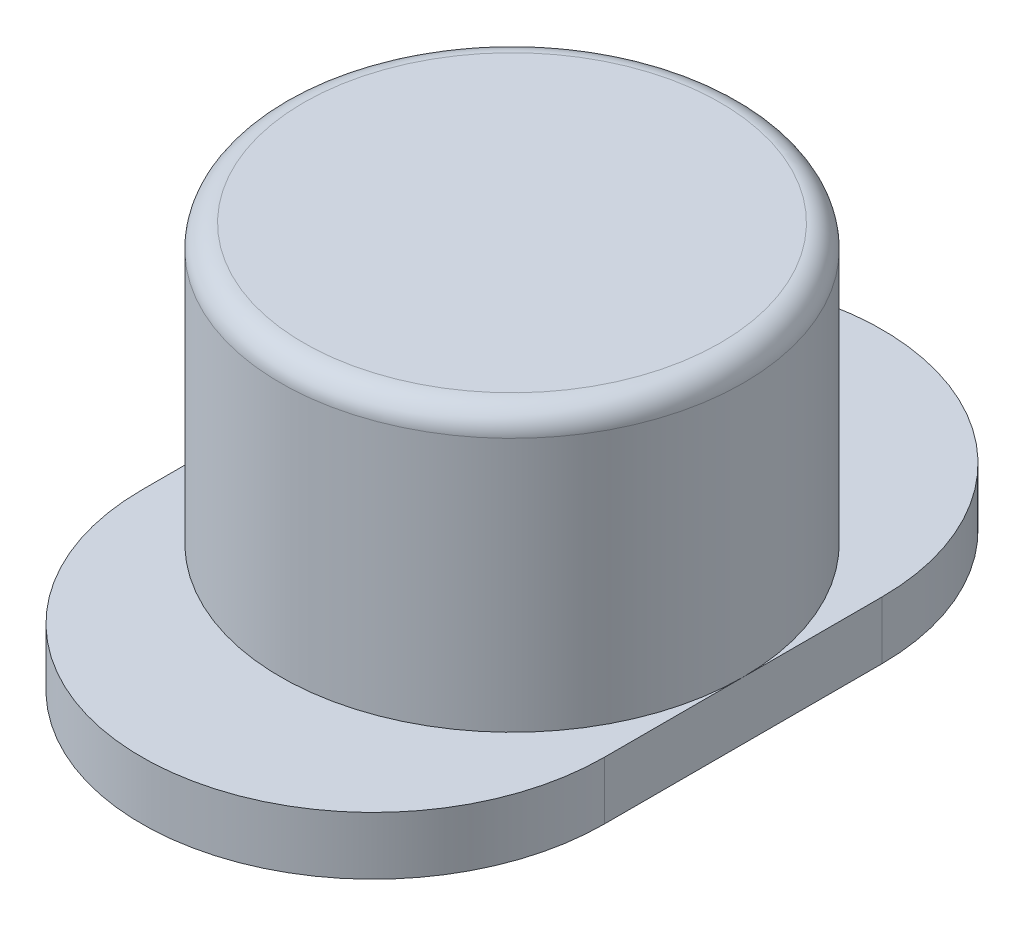
SolidWorks part; units mm, degrees
ref_plane "Front Plane" through (0, 0, 0) normal (0, 0, 1) x (1, 0, 0)
ref_plane "Top Plane" through (0, 0, 0) normal (0, 1, 0) x (1, 0, 0)
ref_plane "Right Plane" through (0, 0, 0) normal (1, 0, 0) x (0, 0, -1)
sketch "Sketch1" plane through (0, 0, 0) normal (0, 0, 1) x (1, 0, 0)
  line L1 (0, 7.25) -> (5, 7.25)
  line L2 (5, 7.25) -> (5, 1.25)
  line L3 (5, 1.25) -> (8, 1.25)
  line L4 (8, 1.25) -> (8, 0)
  line L6 (0, 7.25) -> (0, 6.9292) construction
  line L7 (0, 7.25) -> (0, 0)
  line L10 (0, 0) -> (8, 0)
  dimension "D1" = 5
  dimension "D2" = 3
  dimension "D3" = 6
  dimension "D4" = 1.25
revolve "Revolve1" add sketch "Sketch1" angle 360 about L6
sketch "Sketch2" plane through (0, 0, 0) normal (0, -1, 0) x (1, 0, 0)
  line L1 (-1.75, -1.25) -> (1.75, -1.25)
  line L2 (-1.75, -1.25) -> (-1.75, 1.25)
  line L3 (-1.75, 1.25) -> (1.75, 1.25)
  line L4 (1.75, -1.25) -> (1.75, 1.25)
  line L5 (-1.75, -1.25) -> (1.75, 1.25) construction
  line L6 (-1.75, 1.25) -> (1.75, -1.25) construction
  point P0 (0, 0)
  dimension "D1" = 3.5
  dimension "D2" = 2.5
extrude "Cut-Extrude1" cut sketch "Sketch2" against normal blind 3.5 contours L3 L4 L1 L2
fillet "Fillet1" radius 0.5 1 edges at (-5, 7.25, 0)
sketch "Sketch3" plane through (0, 0, 0) normal (0, 1, 0) x (1, 0, 0)
  line L0 (0, -3) -> (0, 3) construction
  line L1 (-5, -3) -> (-5, 3)
  line L2 (5, -3) -> (5, 3)
  line L3 (0, 3) -> (0, 8) construction
  line L4 (-15, -3) -> (-15, 3)
  line L5 (15, -3) -> (15, 3)
  arc A1 (-5, -3) -> (5, -3) centre (0, -3) ccw
  arc A2 (5, 3) -> (-5, 3) centre (0, 3) ccw
  circle A3 centre (0, 0) radius 8 construction
  circle A4 centre (0, 0) radius 5 construction
  arc A5 (15, 3) -> (-15, 3) centre (0, 3) ccw
  arc A6 (-15, -3) -> (15, -3) centre (0, -3) ccw
  point P5 (0, 0)
  dimension "D1" = 10
extrude "Cut-Extrude2" cut sketch "Sketch3" along normal through all
